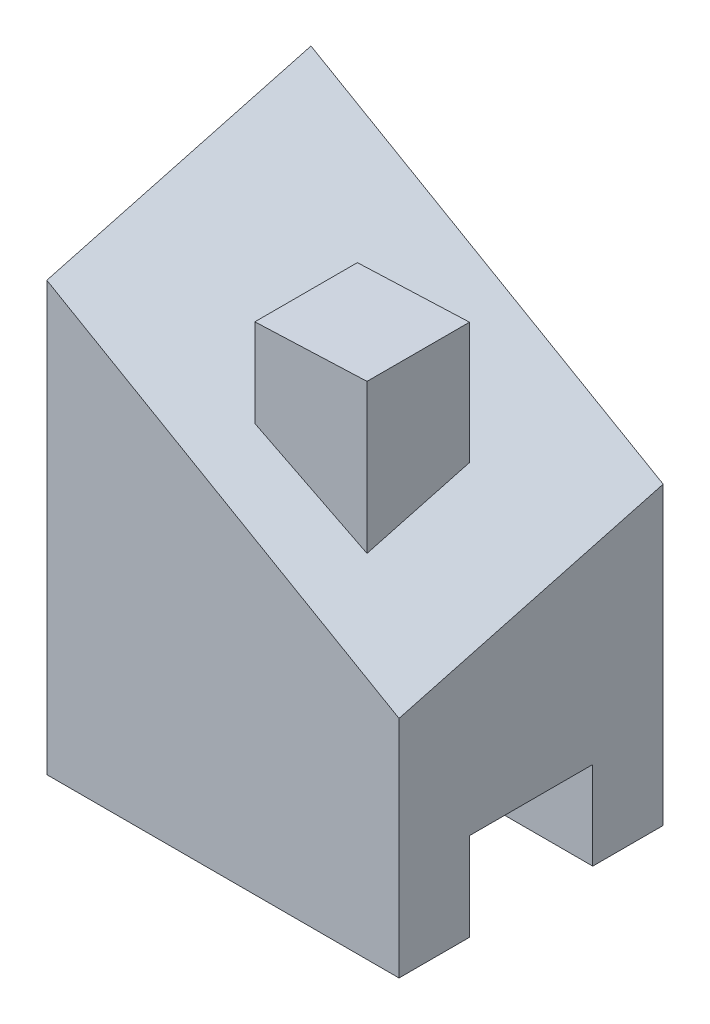
SolidWorks part; units mm, degrees
ref_plane "Front Plane" through (0, 0, 0) normal (0, 0, 1) x (1, 0, 0)
ref_plane "Top Plane" through (0, 0, 0) normal (0, 1, 0) x (1, 0, 0)
ref_plane "Right Plane" through (0, 0, 0) normal (1, 0, 0) x (0, 0, -1)
sketch "Sketch1" plane through (0, 0, 0) normal (0, 1, 0) x (1, 0, 0)
  line L0 (0, 0) -> (60, 0)
  line L1 (60, 0) -> (60, 45)
  line L2 (60, 45) -> (0, 45)
  line L3 (0, 45) -> (0, 0)
  dimension "D1" = 60
  dimension "D2" = 45
extrude "Boss-Extrude1" add sketch "Sketch1" along normal blind 85
sketch "Sketch2" plane through (60, 0, 0) normal (1, 0, 0) x (0, 0, -1)
  line L0 (12, 0) -> (12, 15)
  line L1 (0, 0) -> (45, 0) construction
  line L2 (12, 15) -> (33, 15)
  line L3 (33, 15) -> (33, 0)
  line L4 (33, 0) -> (12, 0)
  dimension "D1" = 12
  dimension "D2" = 12
  dimension "D3" = 15
extrude "Cut-Extrude1" cut sketch "Sketch2" against normal blind 85
sketch "Sketch10" plane through (0, 0, 0) normal (0, 0, 1) x (1, 0, 0)
  line L0 (0, 85) -> (60, 50.359)
  line L1 (60, 85) -> (60, 0) construction
  line L2 (60, 50.359) -> (60, 85)
  line L3 (60, 85) -> (0, 85)
  dimension "D1" = 30
extrude "Cut-Extrude7" cut sketch "Sketch10" against normal blind 53 contours L0 L2 L3
sketch "Sketch15" plane through (60, 0, 0) normal (1, 0, 0) x (0, 0, -1)
  line L0 (45, 50.359) -> (0, 38.3013)
  line L1 (0, 50.359) -> (0, 0) construction
  line L2 (0, 38.3013) -> (0, 50.359)
  line L3 (0, 50.359) -> (45, 50.359)
  dimension "D1" = 15
sketch "Sketch16" plane through (0, 0, 0) normal (-1, 0, 0) x (0, 0, 1)
  line L0 (-45, 85) -> (0, 72.9423)
  line L1 (0, 85) -> (0, 0) construction
  line L2 (0, 72.9423) -> (0, 85)
  line L3 (0, 85) -> (-45, 85)
  dimension "D1" = 15
ref_plane "Plane2" through (29.9711, 51.9114, 13.9096) normal (0.4871, 0.8436, 0.226) x (0.8734, -0.4705, -0.1261)
sketch "Sketch17" plane through (29.9711, 51.9114, 13.9096) normal (0.4871, 0.8436, 0.226) x (0.8734, -0.4705, -0.1261)
  line L0 (34.3829, 56.5005) -> (34.3829, 9.9131)
  line L1 (34.3829, 9.9131) -> (-34.3166, 18.8789)
  line L2 (-34.3166, 18.8789) -> (-34.3166, 65.4663)
  line L3 (-34.3166, 65.4663) -> (34.3829, 56.5005)
extrude "Cut-Extrude9" cut sketch "Sketch16" against normal blind 42
extrude "Cut-Extrude10" cut sketch "Sketch17" along normal blind 42
sketch "Sketch22" plane through (29.9711, 51.9114, 13.9096) normal (0.4871, 0.8436, 0.226) x (0.8734, -0.4705, -0.1261)
  line L0 (-4.3166, 42.6069) -> (16.6834, 40.6578)
  line L1 (16.6834, 40.6578) -> (16.6834, 22.5804)
  line L2 (16.6834, 22.5804) -> (-4.3166, 24.5296)
  line L3 (-4.3166, 24.5296) -> (-4.3166, 42.6069)
  line L4 (-34.3166, 18.8789) -> (34.3829, 9.9131) construction
  line L5 (-34.3166, 65.4663) -> (34.3829, 56.5005) construction
  point P9 (0, 0)
  point P10 (0, 0)
  point P11 (0, 0)
  point P12 (0, 0)
  point P13 (0, 0)
  point P14 (0, 0)
  point P15 (0, 0)
  point P16 (0, 0)
  point P17 (0, 0)
  point P18 (0, 0)
  point P19 (0, 0)
  dimension "D1" = 30
  dimension "D2" = 21
  dimension "D3" = 18
  dimension "D4" = 2.133
  dimension "D5" = 18
ref_plane "Plane3" through (0, 60.2909, 0) normal (0, -1, 0) x (-1, 0, 0)
sketch "Sketch38" plane through (0, 60.2909, 0) normal (0, -1, 0) x (-1, 0, 0)
  line L0 (-26.2011, 9.24) -> (-44.5418, 10.0045)
  line L1 (-44.5418, 10.0045) -> (-44.5418, 27.4659)
  line L2 (-44.5418, 27.4659) -> (-26.2011, 26.7014)
  line L3 (-26.2011, 26.7014) -> (-26.2011, 9.24)
extrude "Boss-Extrude6" add sketch "Sketch38" along normal blind 15 and the other way blind 15
